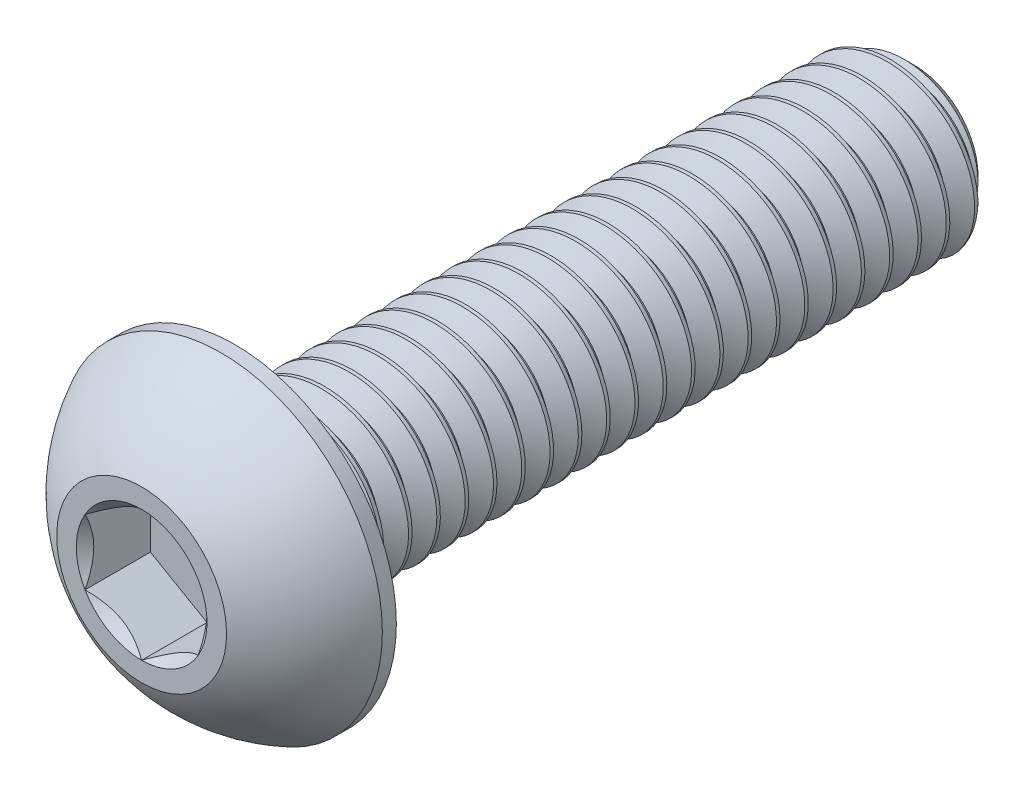
SolidWorks part; units mm, degrees
ref_plane "Front" through (0, 0, 0) normal (0, 0, 1) x (1, 0, 0)
ref_plane "Top" through (0, 0, 0) normal (0, 1, 0) x (1, 0, 0)
ref_plane "Right" through (0, 0, 0) normal (1, 0, 0) x (0, 0, -1)
sketch "Sketch1" plane through (0, 0, 0) normal (1, 0, 0) x (0, 0, -1)
  line L2 (1.65, 1.5) -> (13.65, 1.5)
  line L3 (13.65, 1.5) -> (13.65, 0)
  line L4 (13.65, 0) -> (1.65, 0)
  line L6 (1.4025, 2.85) -> (1.65, 2.85) construction
  line L7 (13.65, 1.5) -> (13.65, -1.5) construction
  line L8 (0, 0) -> (1.65, 0) construction
  line L9 (1.65, 2.85) -> (1.65, -2.85) construction
  line L11 (1.65, 1.5) -> (1.65, 0)
  line L13 (0, 1) -> (0, -1) construction
  line L14 (0, 1) -> (0, 1.5) construction
  arc A3 (0, 1.5) -> (1.4025, 2.85) centre (2.7948, 0) cw construction
  dimension "D1" = 0.2475
  dimension "Head Ht" = 1.65
  dimension "Head Dia" = 5.7
  dimension "Dia" = 3
  dimension "Lg" = 12
  dimension "Hex" = 2
revolve "Revolve1" add sketch "Sketch1" angle 360 mid plane about L4
sketch "Sketch3" plane through (0, 0, -13.65) normal (0, 0, -1) x (-1, 0, 0)
  circle A0 centre (0, 0) radius 1.5
curve "Helix/Spiral1" pitch 0.5 height 12.5 radius 1.5 centre (0, 0, -13.65) axis (0, 0, 1) start towards (0, 1, 0)
sketch "Sketch2" plane through (0, 0, 0) normal (1, 0, 0) x (0, 0, -1)
  line L0 (13.65, 1.5) -> (14.0875, 1.5)
  line L1 (14.0875, 1.5) -> (13.9, 1.1752)
  line L2 (13.9, 1.1752) -> (13.8375, 1.1752)
  line L3 (13.8375, 1.1752) -> (13.65, 1.5)
  line L4 (13.7438, 1.3376) -> (13.9938, 1.3376) construction
  dimension "D1" = 60
  dimension "D2" = 0.0625
  dimension "D3" = 0.25
chamfer "Chamfer1" distance 0.375 angle 45 1 edges at (0, 1.5, -13.65)
sweep "Cut-Sweep1" cut profiles "Sketch2" path "Helix/Spiral1"
sketch "Sketch7" plane through (0, 0, 0) normal (1, 0, 0) x (0, 0, -1)
  line L6 (1.4025, 2.85) -> (1.65, 2.85) construction
  line L8 (0, 0) -> (1.65, 0) construction
  line L11 (1.65, 2.85) -> (1.65, -2.85) construction
  line L12 (1.4025, 2.85) -> (1.65, 2.85)
  line L13 (0, 0) -> (1.65, 0)
  line L14 (0, 1) -> (0, -1) construction
  line L15 (1.65, 2.85) -> (1.65, 0)
  line L16 (0, 1.5) -> (0, 0)
  arc A2 (1.4025, 2.85) -> (0, 1.5) centre (2.7948, 0) ccw construction
  arc A3 (1.4025, 2.85) -> (0, 1.5) centre (2.7948, 0) ccw
revolve "Revolve2" add sketch "Sketch7" angle 360 mid plane about L13
sketch "Sketch5" plane through (0, 0, 0) normal (0, 0, 1) x (1, 0, 0)
  line L1 (1, -0.5774) -> (1, 0.5774)
  line L2 (1, 0.5774) -> (0, 1.1547)
  line L3 (0, 1.1547) -> (-1, 0.5774)
  line L4 (-1, 0.5774) -> (-1, -0.5774)
  line L5 (-1, -0.5774) -> (0, -1.1547)
  line L6 (0, -1.1547) -> (1, -0.5774)
  circle A0 centre (0, 0) radius 1 construction
extrude "Cut-Extrude2" cut sketch "Sketch5" against normal blind 1.155
sketch "Sketch6" plane through (0, 0, 0) normal (0, 0, 1) x (1, 0, 0)
  circle A0 centre (0, 0) radius 1.1547
extrude "Cut-Extrude3" cut sketch "Sketch6" against normal blind 1.155 draft 45
sketch "Sketch9" [suppressed] plane through (0, 0, -4.2164) normal (0, 0, 1) x (1, 0, 0)
  circle A2 centre (0, 0) radius 3.9687
extrude "Boss-Extrude2" [suppressed] add sketch "Sketch9" against normal offset from surface (9.525 mm away) 28.575
sketch "Sketch10" plane through (0, 0, 0) normal (1, 0, 0) x (0, 0, -1)
  line L0 (13.65, 1.5) -> (13.65, -1.5) construction
  point P0 (12.9, -1.5)
  dimension "D1" = 0.75
equation "\"D3@Helix/Spiral1\" = \"Lg@Sketch1\" + \"D4@Helix/Spiral1\""
equation "\"D2@Sketch2\" = \"D4@Helix/Spiral1\" * .125"
equation "\"D3@Sketch2\" = \"D4@Helix/Spiral1\" * .5"
equation "\"D1@Chamfer1\" = \"D4@Helix/Spiral1\" * .75"
equation "\"D1@Cut-Extrude2\" = \"Head Ht@Sketch1\" * .7"
equation "\"D1@Sketch1\" = \"Head Ht@Sketch1\" * .15"
equation "\"D1@Sketch10\" = \"D4@Helix/Spiral1\" * 1.5"
equation "\"D1@Cut-Extrude3\" = \"D1@Cut-Extrude2\""
